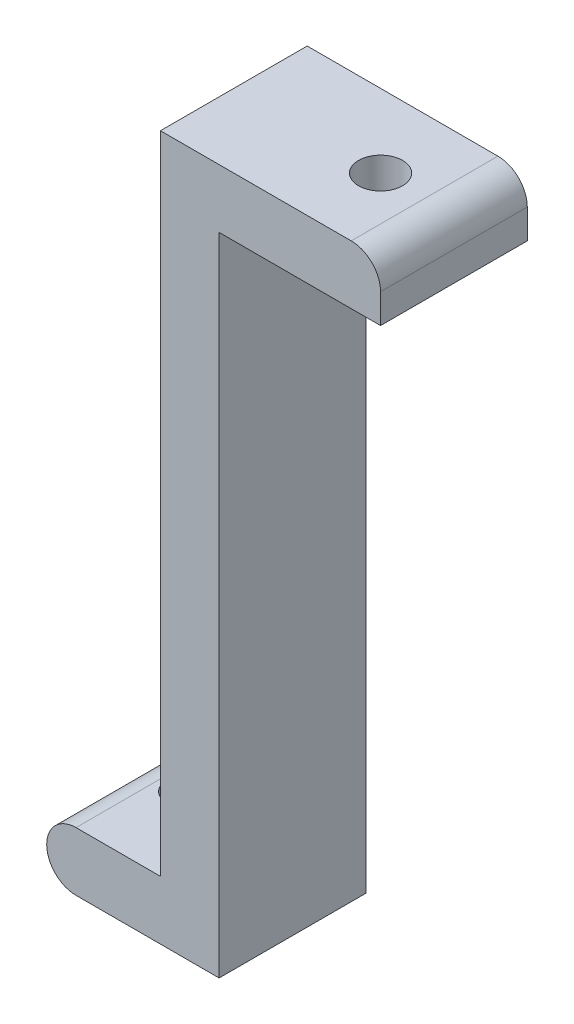
SolidWorks part; units mm, degrees
ref_plane "Front Plane" through (0, 0, 0) normal (0, 0, 1) x (1, 0, 0)
ref_plane "Top Plane" through (0, 0, 0) normal (0, 1, 0) x (1, 0, 0)
ref_plane "Right Plane" through (0, 0, 0) normal (1, 0, 0) x (0, 0, -1)
sketch "Sketch1" plane through (0, 0, 0) normal (0, 0, 1) x (1, 0, 0)
  line L0 (0, 0) -> (-15, 0)
  line L1 (-15, 0) -> (-15, -44)
  line L2 (-15, -44) -> (-22.75, -44)
  line L3 (-22.75, -44) -> (-22.75, -48)
  line L4 (-22.75, -48) -> (-11, -48)
  line L5 (-11, -48) -> (-11, -4)
  line L6 (-11, -4) -> (0, -4)
  line L7 (0, -4) -> (0, 0)
  dimension "D1" = 4
  dimension "D2" = 4
  dimension "D3" = 4
  dimension "D4" = 44
  dimension "D5" = 11.75
  dimension "D6" = 11
extrude "Boss-Extrude1" add sketch "Sketch1" along normal blind 10
sketch "Sketch2" plane through (0, -44, 0) normal (0, 1, 0) x (1, 0, 0)
  line L0 (-22.75, -10) -> (-22.75, 0) construction
  circle A0 centre (-19, -4) radius 1.5
  point P4 (-22.75, -5)
  dimension "D1" = 3
  dimension "D2" = 3.75
  dimension "D3" = 1
extrude "Cut-Extrude1" cut sketch "Sketch2" against normal blind 10
sketch "Sketch3" plane through (0, -4, 0) normal (0, -1, 0) x (-1, 0, 0)
  line L0 (0, -10) -> (0, 0) construction
  circle A0 centre (5, -5) radius 1.5
  point P4 (0, -5)
  dimension "D1" = 3
  dimension "D2" = 0
  dimension "D3" = 5
extrude "Cut-Extrude2" cut sketch "Sketch3" against normal blind 10
fillet "Fillet1" radius 2 1 edges at (0, 0, 5)
fillet "Fillet2" radius 2 2 edges at (-22.75, -48, 5) (-22.75, -44, 5)
